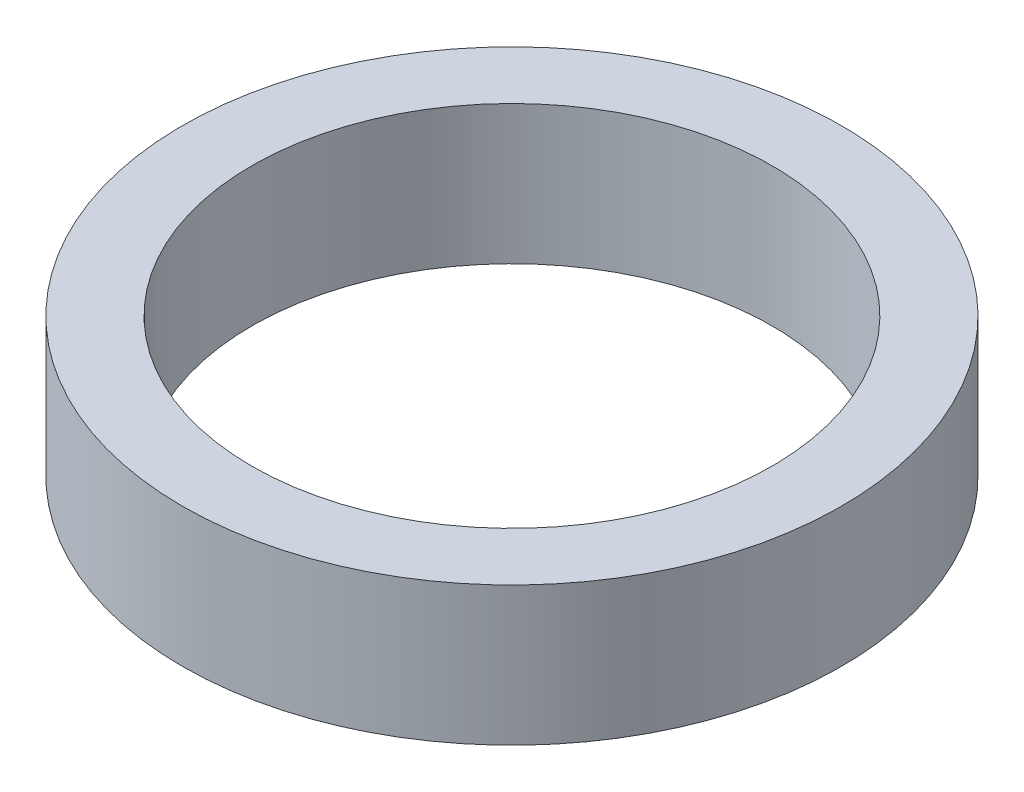
SolidWorks part; units mm, degrees
ref_plane "Front Plane" through (0, 0, 0) normal (0, 0, 1) x (1, 0, 0)
ref_plane "Top Plane" through (0, 0, 0) normal (0, 1, 0) x (1, 0, 0)
ref_plane "Right Plane" through (0, 0, 0) normal (1, 0, 0) x (0, 0, -1)
sketch "Sketch1" plane through (0, 0, 0) normal (0, 1, 0) x (1, 0, 0)
  circle A0 centre (0, 0) radius 47.5
  dimension "FLANGE_OD" = 95
extrude "Boss-Extrude1" add sketch "Sketch1" along normal blind 20
sketch "Sketch2" plane through (0, 0, 0) normal (0, 1, 0) x (1, 0, 0)
  circle A0 centre (0, 0) radius 37.5
  dimension "BORE_D" = 75
extrude "Cut-Extrude1" cut sketch "Sketch2" along normal through all
sketch "Sketch3" plane through (0, 20, 0) normal (0, 1, 0) x (1, 0, 0)
  circle A0 centre (0, 0) radius 21.8776 construction
  circle A1 centre (-21.8776, 0) radius 1.7867
  dimension "BOLT_D" = 3.5734
  dimension "BOLT_PCD" = 43.7553
extrude "Cut-Extrude2" cut sketch "Sketch3" against normal blind 19.8666 rebuild error yes
pattern_circular "CirPattern1" count 8 over 360 rebuild error yes
